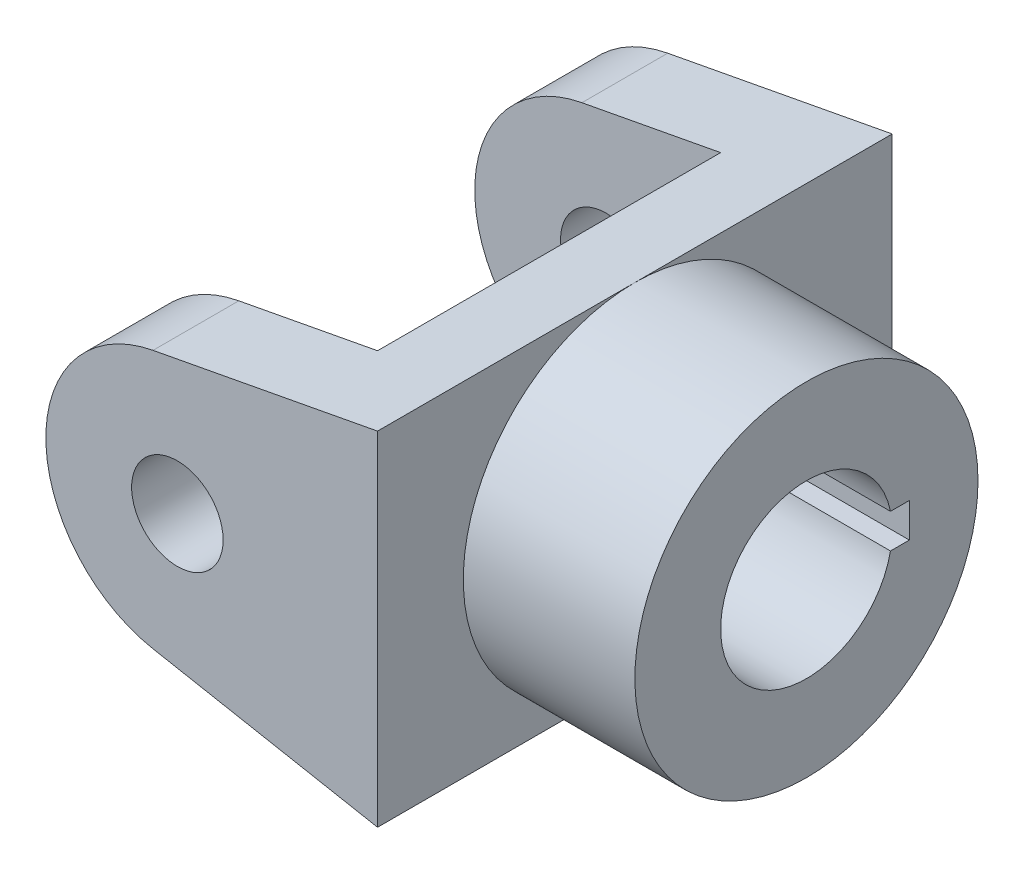
SolidWorks part; units mm, degrees
ref_plane "Front Plane" through (0, 0, 0) normal (0, 0, 1) x (1, 0, 0)
ref_plane "Top Plane" through (0, 0, 0) normal (0, 1, 0) x (1, 0, 0)
ref_plane "Right Plane" through (0, 0, 0) normal (1, 0, 0) x (0, 0, -1)
sketch "Sketch1" plane through (0, 0, 0) normal (0, 1, 0) x (1, 0, 0)
  line L1 (-44, 45) -> (44, 45)
  line L2 (-44, 45) -> (-44, -45)
  line L3 (-44, -45) -> (44, -45)
  line L4 (44, 45) -> (44, -45)
  line L5 (-44, 45) -> (44, -45) construction
  line L6 (-44, -45) -> (44, 45) construction
  point P0 (0, 0)
  dimension "D1" = 88
  dimension "D2" = 90
extrude "Boss-Extrude1" add sketch "Sketch1" along normal blind 60
sketch "Sketch2" plane through (0, 60, 0) normal (0, 1, 0) x (1, 0, 0)
  line L0 (48.2684, 0) -> (-48.2684, 0) construction
  line L1 (-44, 45) -> (-44, -45) construction
  line L2 (44, -45) -> (44, 45) construction
  line L3 (-1, 30) -> (-44, 30)
  line L4 (44, -45) -> (44, 45)
  line L5 (-1, -30) -> (-1, 30)
  line L6 (-1, -45) -> (-1, 45) construction
  line L7 (-1, -30) -> (-44, -30)
  line L8 (-44, 30) -> (-44, -30)
  line L9 (14, -45) -> (14, 45)
  line L13 (14, 45) -> (-59, 45) construction
  line L14 (-59, 45) -> (-59, -45) construction
  line L15 (14, -45) -> (-59, -45) construction
  line L16 (-44, -45) -> (44, -45) construction
  line L17 (14, -45) -> (44, -45)
  line L18 (14, 45) -> (44, 45)
  point P4 (0, 0)
  point P13 (-1, 0)
  dimension "D2" = 15
  dimension "D1" = 43
extrude "Cut-Extrude1" cut sketch "Sketch2" against normal blind 60
sketch "Sketch3" plane through (0, 0, 45) normal (0, 0, 1) x (1, 0, 0)
  line L0 (14, 0) -> (14, 60) construction
  line L1 (-44, 0) -> (14, 0) construction
  line L2 (-25.259, 52.6022) -> (14, 60)
  line L3 (-25.259, 7.3978) -> (14, 0)
  circle A0 centre (-21, 30) radius 8
  arc A1 (-25.259, 52.6022) -> (-25.259, 7.3978) centre (-21, 30) ccw
  line M3 (-44, 0) -> (14, 0)
  line M5 (14, 60) -> (-44, 60)
  line M6 (-44, 60) -> (-44, 0)
  dimension "D1" = 16
  dimension "D3" = 46
  dimension "D2" = 35
  dimension "D4" = 30
extrude "Cut-Extrude2" cut sketch "Sketch3" against normal blind 125 contours A1 L3 M6 M3 | A1 L2 M5 M6 | A0 region at (-27.5034, 54.3725, 45) region at (-27.5034, 5.6275, 45) region at (-21, 30, 45)
sketch "Sketch4" plane through (14, 0, 0) normal (1, 0, 0) x (0, 0, -1)
  line L0 (-45, 0) -> (-45, 60) construction
  line L1 (45, 0) -> (-45, 0) construction
  line L2 (45, 60) -> (-45, 60) construction
  line L3 (14.6969, 33) -> (18, 33)
  line L4 (14.6969, 27) -> (18, 27)
  line L8 (18, 33) -> (18, 27)
  circle A0 centre (0, 30) radius 30
  arc A1 (14.6969, 33) -> (14.6969, 27) centre (0, 30) ccw
  dimension "D1" = 60
  dimension "D2" = 30
  dimension "D3" = 45
  dimension "D4" = 30
  dimension "D7" = 18
  dimension "D5" = 59.6969
  dimension "D6" = 59.6969
  dimension "D8" = 27
  dimension "D9" = 33
extrude "Cut-Extrude3" cut sketch "Sketch4" against normal blind 30 contours L3 A1 L4 L8 region at (14, 30, -0.4218)
extrude "Boss-Extrude2" add sketch "Sketch4<4>" along normal blind 30
sketch "Sketch4<4>" plane through (14, 0, 0) normal (1, 0, 0) x (0, 0, -1) same geometry as "Sketch4"
